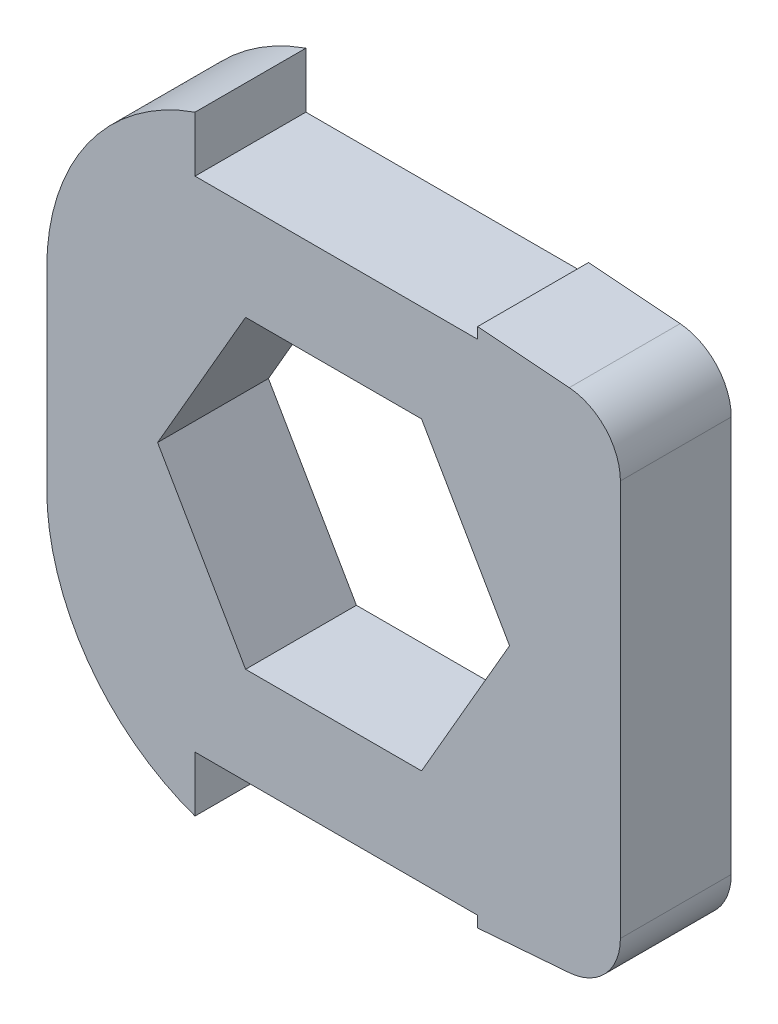
SolidWorks part; units mm, degrees
ref_plane "Plan de face" through (0, 0, 0) normal (0, 0, 1) x (1, 0, 0)
ref_plane "Plan de dessus" through (0, 0, 0) normal (0, 1, 0) x (1, 0, 0)
ref_plane "Plan de droite" through (0, 0, 0) normal (1, 0, 0) x (0, 0, -1)
sketch "Esquisse1" plane through (0, 0, 0) normal (0, 0, 1) x (1, 0, 0)
  line L0 (0, 5.5) -> (2.6754, 5.5)
  line L1 (2.6754, 5.5) -> (2.6754, 4.5)
  line L2 (2.6754, 4.5) -> (10.3509, 4.5) construction
  line L3 (10.3509, 4.5) -> (10.3509, -4.5)
  line L4 (10.3509, -4.5) -> (2.6754, -4.5) construction
  line L5 (2.6754, -4.5) -> (2.6754, -5.5)
  line L6 (2.6754, -5.5) -> (0, -5.5)
  line L7 (0, -5.5) -> (0, 5.5)
  line L8 (0, 0) -> (10.3509, 0) construction
  line L9 (10.3509, 4.5) -> (7.7754, 4.7)
  line L10 (2, 0) -> (3.5877, -2.75)
  line L11 (3.5877, -2.75) -> (6.7631, -2.75)
  line L12 (6.7631, -2.75) -> (8.3509, 0)
  line L13 (8.3509, 0) -> (6.7631, 2.75)
  line L14 (6.7631, 2.75) -> (3.5877, 2.75)
  line L15 (3.5877, 2.75) -> (2, 0)
  line L16 (7.7754, 4.7) -> (7.7754, 4.5)
  line L17 (7.7754, 4.5) -> (2.6754, 4.5)
  line L18 (7.7754, -4.5) -> (2.6754, -4.5)
  line L19 (7.7754, -4.7) -> (7.7754, -4.5)
  line L20 (10.3509, -4.5) -> (7.7754, -4.7)
  circle A0 centre (5.1754, 0) radius 2.75 construction
  dimension "D1" = 5.5
  dimension "D2" = 1.75
  dimension "D3" = 2.5
  dimension "D4" = 2
  dimension "D5" = 1
  dimension "D6" = 2
  dimension "D7" = 6.3509
  dimension "D8" = 5.1
  dimension "D9" = 0.2
  dimension "D10" = 9
extrude "Boss.-Extru.1" add sketch "Esquisse1" along normal blind 2
fillet "Congé1" radius 4 2 edges at (0, -5.5, 1) (0, 5.5, 1)
fillet "Congé2" radius 1 2 edges at (10.3509, -4.5, 1) (10.3509, 4.5, 1)
